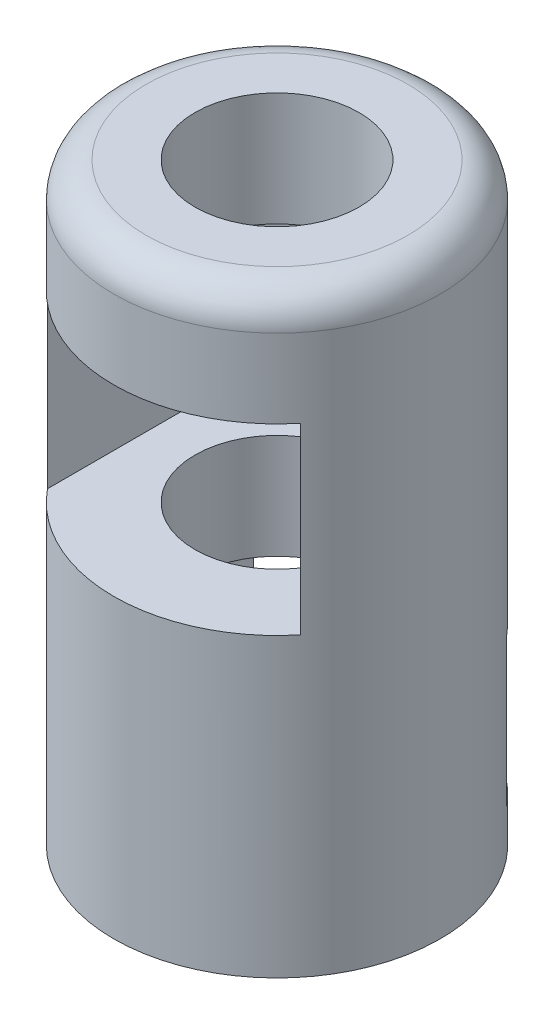
SolidWorks part; units mm, degrees
ref_plane "Front Plane" through (0, 0, 0) normal (0, 0, 1) x (1, 0, 0)
ref_plane "Top Plane" through (0, 0, 0) normal (0, 1, 0) x (1, 0, 0)
ref_plane "Right Plane" through (0, 0, 0) normal (1, 0, 0) x (0, 0, -1)
sketch "Sketch1" plane through (0, 0, 0) normal (0, 1, 0) x (1, 0, 0)
  circle A0 centre (0, 0) radius 9.35
  circle A1 centre (0, 0) radius 7.5
  dimension "D1" = 18.7
  dimension "D2" = 15
extrude "Boss-Extrude1" add sketch "Sketch1" along normal blind 34
fillet "Fillet1" radius 2 1 edges at (0, 34, 9.35)
ref_plane "Plane1" through (0, 11, 0) normal (0, 1, 0) x (1, 0, 0)
sketch "Sketch2" plane through (0, 0, 0) normal (0, -1, 0) x (-1, 0, 0)
  circle A0 centre (0, 0) radius 7.5
extrude "Boss-Extrude2" add sketch "Sketch2" against normal blind 34
sketch "Sketch3" plane through (0, 0, 0) normal (0, -1, 0) x (-1, 0, 0)
  circle A1 centre (0, 0) radius 4.7
  dimension "D1" = 9.4
extrude "Cut-Extrude1" cut sketch "Sketch3" against normal blind 40
sketch "Sketch4" plane through (0, 11, 0) normal (0, 1, 0) x (1, 0, 0)
  line L1 (0, -8.3716) -> (7.25, -4.1858)
  line L2 (7.25, -4.1858) -> (7.25, 4.1858)
  line L3 (7.25, 4.1858) -> (0, 8.3716)
  line L4 (0, 8.3716) -> (-7.25, 4.1858)
  line L5 (-7.25, 4.1858) -> (-7.25, -4.1858)
  line L6 (-7.25, -4.1858) -> (0, -8.3716)
  circle A0 centre (0, 0) radius 7.25 construction
  dimension "D1" = 14.5
extrude "Cut-Extrude2" cut sketch "Sketch4" against normal blind 8.5
sketch "Sketch5" plane through (0, 0, 0) normal (0, 0, 1) x (1, 0, 0)
  line L0 (0, -1.5413) -> (0, 31.7188) construction
  line L1 (10.285, 11) -> (-10.285, 11) construction
  line L2 (7.25, 2.5) -> (-7.25, 2.5)
  line L3 (7.25, 2.5) -> (7.25, 11)
  line L4 (7.25, 11) -> (-7.25, 11)
  line L5 (-7.25, 2.5) -> (-7.25, 11)
  line L6 (7.25, 2.5) -> (-7.25, 11) construction
  line L7 (7.25, 11) -> (-7.25, 2.5) construction
  line L8 (-9.35, 0) -> (9.35, 0) construction
  point P3 (0, 6.75)
  dimension "D1" = 0
  dimension "D2" = 2.5
  dimension "D3" = 14.5
extrude "Cut-Extrude3" cut sketch "Sketch5" against normal blind 10
ref_plane "Plane2" through (0, 17, 0) normal (0, 1, 0) x (1, 0, 0)
sketch "Sketch6" plane through (0, 17, 0) normal (0, 1, 0) x (1, 0, 0)
  line L2 (7.25, -4.1858) -> (7.25, 4.1858)
  line L3 (7.25, 4.1858) -> (0, 8.3716)
  line L4 (0, 8.3716) -> (-7.25, 4.1858)
  line L5 (-7.25, 4.1858) -> (-7.25, -4.1858)
  line L7 (7.25, 4.1858) -> (-7.25, 4.1858)
  line L12 (7.25, -4.1858) -> (7.25, -13.8409)
  line L13 (7.25, -13.8409) -> (-7.25, -13.8409)
  line L14 (-7.25, -4.1858) -> (-7.25, -13.8409)
  line L15 (0, -8.3716) -> (7.25, -4.1858) [skipped]
  line L16 (-7.25, -4.1858) -> (0, -8.3716) [skipped]
  circle A0 centre (0, 0) radius 7.25 construction
  dimension "D1" = 14.5
extrude "Cut-Extrude10" cut sketch "Sketch6" along normal blind 10.5 contours L5 L14 L13 L12 L2 L7 | L7 L3 L4 region at (0, 17, 1.1162) region at (0, 17, 9.9632) region at (0, 17, -5.5811)
